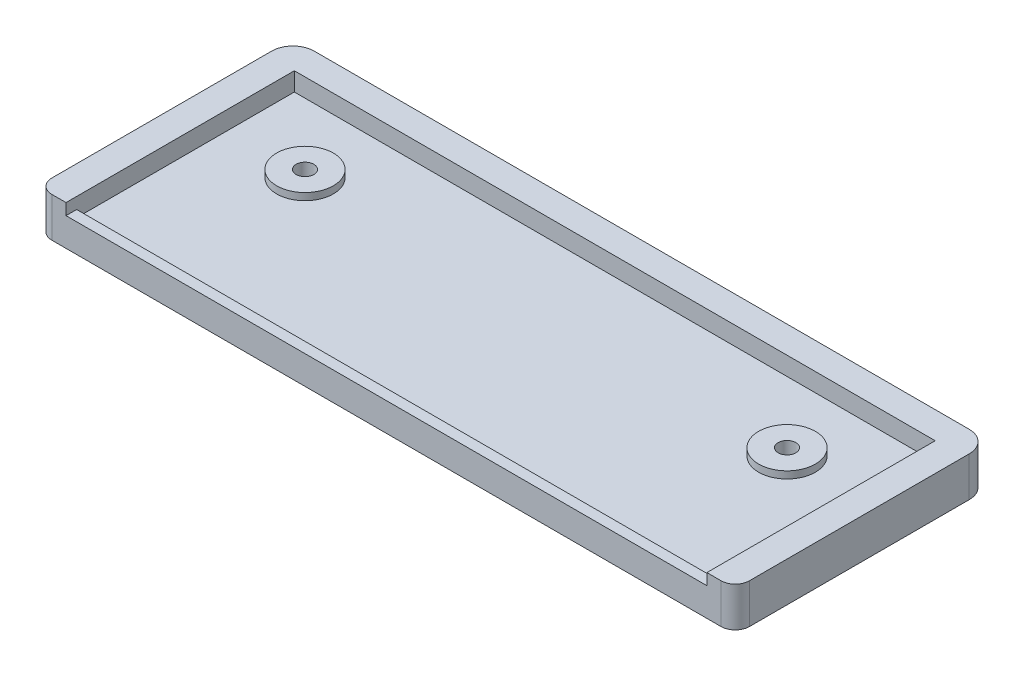
SolidWorks part; units mm, degrees
ref_plane "Front Plane" through (0, 0, 0) normal (0, 0, 1) x (1, 0, 0)
ref_plane "Top Plane" through (0, 0, 0) normal (0, 1, 0) x (1, 0, 0)
ref_plane "Right Plane" through (0, 0, 0) normal (1, 0, 0) x (0, 0, -1)
sketch "Sketch1" plane through (0, 0, 0) normal (0, 1, 0) x (1, 0, 0)
  line L0 (0, -32) -> (-0.2, -32)
  line L1 (0, 0) -> (89.98, 0)
  line L2 (0, 0) -> (0, -32)
  line L3 (0, -32) -> (89.98, -32)
  line L4 (89.98, 0) -> (89.98, -32)
  line L5 (-0.2, -32) -> (-0.2, 0.2)
  line L6 (-0.2, 0.2) -> (90.18, 0.2)
  line L7 (90.18, 0.2) -> (90.18, -32)
  line L8 (90.18, -32) -> (89.98, -32)
  line L9 (-0.2, -32) -> (-2.2, -32)
  line L10 (-4.2, -30) -> (-4.2, 1)
  line L11 (-1.2, 4) -> (91.18, 4)
  line L12 (94.18, 1) -> (94.18, -30)
  line L13 (92.18, -32) -> (90.18, -32)
  circle A0 centre (78.98, -9.5) radius 1.25
  circle A1 centre (11, -9.5) radius 1.25
  arc A2 (91.18, 4) -> (94.18, 1) centre (91.18, 1) cw
  arc A3 (-4.2, 1) -> (-1.2, 4) centre (-1.2, 1) cw
  arc A4 (94.18, -30) -> (92.18, -32) centre (92.18, -30) cw
  arc A5 (-2.2, -32) -> (-4.2, -30) centre (-2.2, -30) cw
  circle A6 centre (11, -9.5) radius 4
  circle A7 centre (78.98, -9.5) radius 4
  point P23 (94.18, -32)
  point P26 (-4.2, -32)
  dimension "D6" = 2.5
  dimension "D7" = 2.5
  dimension "D14" = 3
  dimension "D15" = 2
  dimension "D16" = 8
  dimension "D17" = 8
  dimension "D1" = 89.98
  dimension "D2" = 32
  dimension "D3" = 11
  dimension "D4" = 11
  dimension "D5" = 9.5
  dimension "D8" = 0.2
  dimension "D9" = 0.2
  dimension "D10" = 0.2
  dimension "D11" = 4
  dimension "D12" = 4
  dimension "D13" = 4
extrude "Boss-Extrude1" add sketch "Sketch1" along normal blind 3 contours L4 L1 L2 L3 A7 A6 | A6 A1 | L8 L7 L6 L5 L0 L2 L1 L4 | A5 L9 L5 L6 L7 L13 A4 L12 A2 L11 A3 L10 | A7 A0 region at (-0.1, 0, 31.0406) region at (44.99, 0, 16.2352) region at (-1.2, 0, 30.9524) region at (7.1131, 0, 9.5) region at (75.0931, 0, 9.5)
extrude "Boss-Extrude2" add sketch "Sketch1<5>" along normal blind 1 from surface contours A6 A1 | A5 L9 L5 L6 L7 L13 A4 L12 A2 L11 A3 L10 | A7 A0 region at (-1.2, 0, 30.9524) region at (7.1131, 0, 9.5) region at (75.0931, 0, 9.5) starting at face at (44.99, 3, 14.1982)
sketch "Sketch1<5>" plane through (0, 0, 0) normal (0, 1, 0) x (1, 0, 0) same geometry as "Sketch1"
extrude "Boss-Extrude3" add sketch "Sketch1<6>" along normal blind 1.6 from surface contours A5 L9 L5 L6 L7 L13 A4 L12 A2 L11 A3 L10 region at (-1.2, 0, 30.9524) starting at face at (44.99, 4, 14.7655)
sketch "Sketch1<6>" plane through (0, 0, 0) normal (0, 1, 0) x (1, 0, 0) same geometry as "Sketch1"
sketch "Sketch2" plane through (0, 3, 0) normal (0, 1, 0) x (1, 0, 0)
  line L0 (90.18, -32) -> (90.18, 0.2) construction
  line L1 (-0.2, -32) -> (90.18, -32)
  line L2 (-0.2, -32) -> (-0.2, -30.5)
  line L3 (-0.2, -30.5) -> (90.18, -30.5)
  line L4 (90.18, -32) -> (90.18, -30.5)
  dimension "D1" = 1.5
extrude "Boss-Extrude4" add sketch "Sketch2" along normal blind 1
